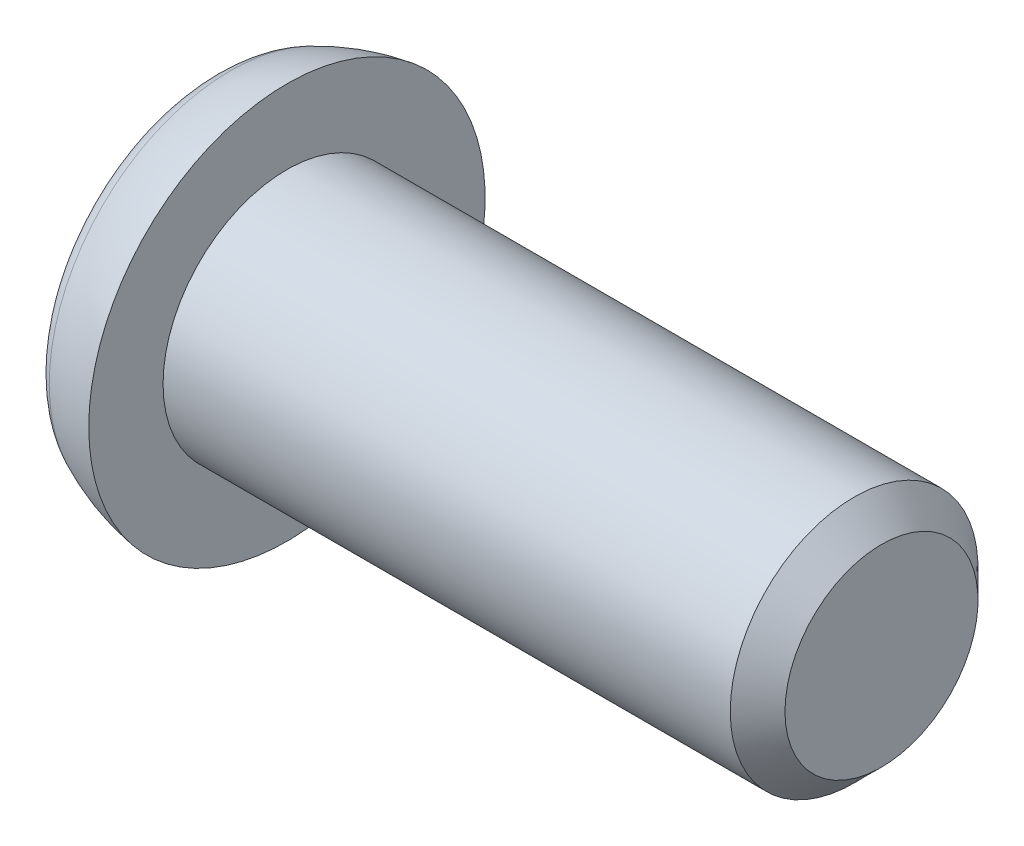
SolidWorks part; units mm, degrees
ref_plane "Front Plane" through (0, 0, 0) normal (0, 0, 1) x (1, 0, 0)
ref_plane "Top Plane" through (0, 0, 0) normal (0, 1, 0) x (1, 0, 0)
ref_plane "Right Plane" through (0, 0, 0) normal (1, 0, 0) x (0, 0, -1)
ref_plane "Plane1" through (0, 0, 0) normal (0, 0, 1) x (1, 0, 0)
sketch "Sketch1" plane through (0, 0, 0) normal (0, 0, 1) x (1, 0, 0)
  line L0 (-0.8, 0) -> (-0.8, 1.466)
  line L1 (0, 2) -> (0, 1.25)
  line L2 (0, 1.25) -> (5.724, 1.25)
  line L3 (5.724, 1.25) -> (6, 0.974)
  line L4 (6, 0.974) -> (6, 0)
  line L5 (6, 0) -> (-0.8, 0)
  line L6 (6, 0) -> (-0.8, 0) construction
  arc A0 (-0.8, 1.466) -> (-0.5715, 1.8274) centre (-0.4, 1.466) cw
  arc A1 (-0.5715, 1.8274) -> (0, 2) centre (0.286, 0.0206) cw
revolve "Revolve1" add sketch "Sketch1" angle 360 about L6 reverse direction yes
ref_plane "Plane2" through (0, 0, 0) normal (0, 0, 1) x (1, 0, 0)
sketch "Sketch2" plane through (0, 0, 0) normal (0, 0, 1) x (1, 0, 0)
  line L0 (-0.8, 1) -> (-0.8, -1)
  arc A0 (-0.8, -1) -> (0.32, 0) centre (-1.181, 0.554) ccw
  arc A1 (0.32, 0) -> (-0.8, 1) centre (-1.181, -0.554) ccw
extrude "Cut-Extrude1" cut sketch "Sketch2" against normal blind 0.2 and the other way blind 0.2
ref_plane "Plane3" through (0, 0, 0) normal (0, 1, 0) x (1, 0, 0)
sketch "Sketch3" plane through (0, 0, 0) normal (0, 1, 0) x (1, 0, 0)
  line L0 (-0.8, 1) -> (-0.8, -1)
  arc A0 (-0.8, -1) -> (0.32, 0) centre (-1.181, 0.554) ccw
  arc A1 (0.32, 0) -> (-0.8, 1) centre (-1.181, -0.554) ccw
extrude "Cut-Extrude2" cut sketch "Sketch3" against normal blind 0.2 and the other way blind 0.2
